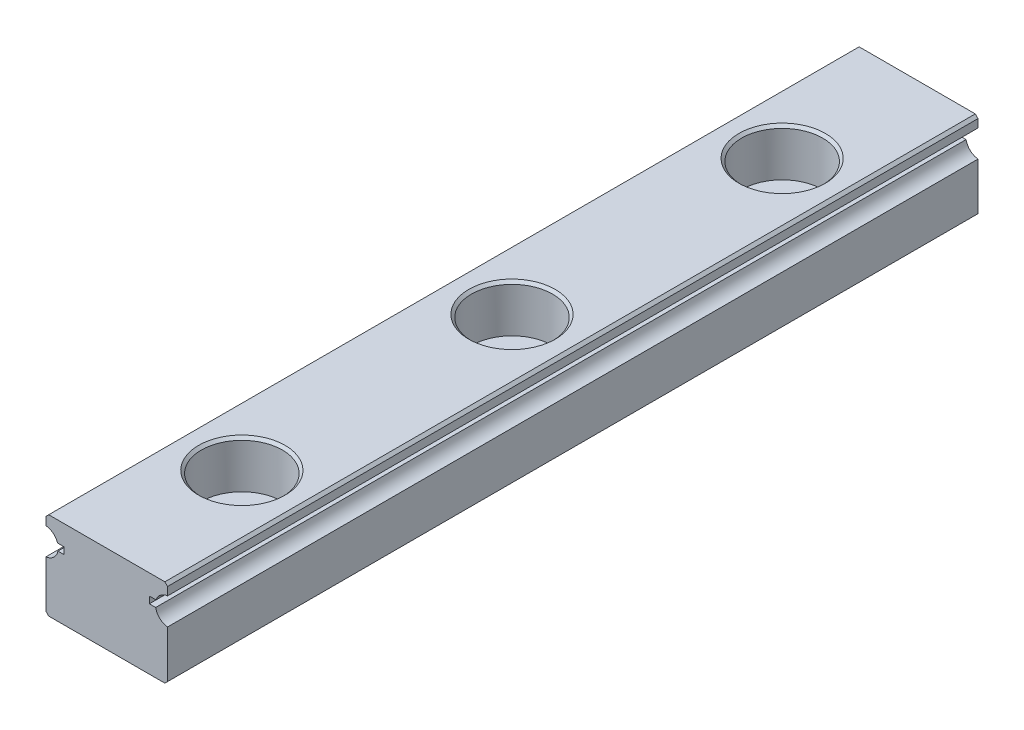
SolidWorks part; units mm, degrees
ref_plane "Спереди" through (0, 0, 0) normal (0, 0, 1) x (1, 0, 0)
ref_plane "Сверху" through (0, 0, 0) normal (0, 1, 0) x (1, 0, 0)
ref_plane "Справа" through (0, 0, 0) normal (1, 0, 0) x (0, 0, -1)
sketch "Sketch1" plane through (0, 0, 0) normal (0, 0, 1) x (1, 0, 0)
  line L0 (0, 0) -> (0, 4.3706) construction
  line L1 (-4.3, -3.25) -> (4.3, -3.25)
  line L2 (-4.5, -3.05) -> (-4.5, 0.455)
  line L3 (-4.3, 3.25) -> (4.3, 3.25)
  line L4 (4.5, -3.05) -> (4.5, 0.455)
  line L5 (-4.5, -3.25) -> (4.5, 3.25) construction
  line L6 (-4.5, 3.25) -> (4.5, -3.25) construction
  line L7 (-4.5, 2.445) -> (-4.5, 3.05)
  line L8 (4.5, 2.445) -> (4.5, 3.05)
  line L9 (-4.5, -3.05) -> (-4.3, -3.25)
  line L10 (4.3, -3.25) -> (4.5, -3.05)
  line L11 (4.3, 3.25) -> (4.5, 3.05)
  line L12 (-4.5, 3.05) -> (-4.3, 3.25)
  line L13 (3.6177, 1.2625) -> (3.1501, 1.2625)
  line L14 (-3.6177, 1.2625) -> (-3.1501, 1.2625)
  line L15 (3.1501, 1.2625) -> (3.1501, 1.7625)
  line L16 (-3.6501, 1.7625) -> (-3.1501, 1.7625)
  line L17 (-3.1501, 1.2625) -> (-3.1501, 1.7625)
  line L18 (3.6501, 1.7625) -> (3.1501, 1.7625)
  arc A0 (-4.5, 2.445) -> (-3.6501, 1.7625) centre (-4.6, 1.45) cw
  arc A1 (4.5, 2.445) -> (3.6501, 1.7625) centre (4.6, 1.45) ccw
  arc A2 (-3.6177, 1.2625) -> (-4.5, 0.455) centre (-4.6, 1.45) cw
  arc A3 (3.6177, 1.2625) -> (4.5, 0.455) centre (4.6, 1.45) ccw
  point P0 (0, 0)
  dimension "D4" = 1
  dimension "D5" = 0.1
  dimension "D1" = 9
  dimension "D2" = 6.5
  dimension "D3" = 1.8
  dimension "D6" = 0.5
  dimension "D7" = 0.5
extrude "Extrude1" add sketch "Sketch1" along normal blind 60
sketch "Sketch2" plane through (0, 3.25, 0) normal (0, 1, 0) x (1, 0, 0)
  line L0 (0, 0) -> (0, -10) construction
  circle A0 centre (0, -10) radius 1.75
  circle A1 centre (0, -10) radius 3
  dimension "D1" = 3.5
  dimension "D2" = 6
  dimension "D3" = 10
extrude "Extrude2" cut sketch "Sketch2" against normal up to next contours A0 region at (0, 3.25, 10)
extrude "Extrude4" cut sketch "Sketch" against normal blind 3.5
sketch "Sketch" plane through (0, 3.25, 0) normal (0, 1, 0) x (1, 0, 0) same geometry as "Sketch2"
chamfer "Chamfer1" distance 0.2 angle 45 2 edges at (0, -3.25, 11.75) (0, 3.25, 13)
pattern_linear "LPattern1" count 3 spacing 20 along (0, 0, 1) of "Extrude4", "Chamfer1", "Extrude2"
